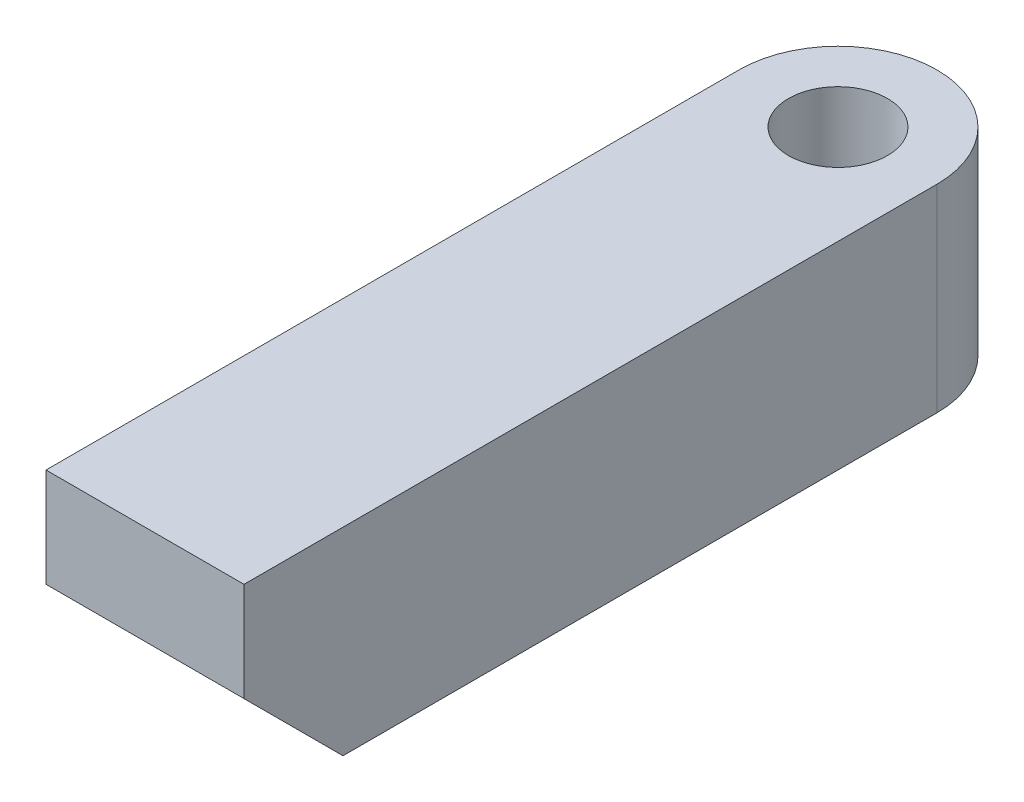
SolidWorks part; units mm, degrees
ref_plane "Front Plane" through (0, 0, 0) normal (0, 0, 1) x (1, 0, 0)
ref_plane "Top Plane" through (0, 0, 0) normal (0, 1, 0) x (1, 0, 0)
ref_plane "Right Plane" through (0, 0, 0) normal (1, 0, 0) x (0, 0, -1)
sketch "Sketch1" plane through (0, 0, 0) normal (0, 1, 0) x (1, 0, 0)
  line L1 (-5, -20) -> (5, -20)
  line L2 (-5, -20) -> (-5, 20)
  line L3 (-5, 20) -> (5, 20)
  line L4 (5, -20) -> (5, 20)
  line L5 (-5, -20) -> (5, 20) construction
  line L6 (-5, 20) -> (5, -20) construction
  point P0 (0, 0)
  dimension "D1" = 40
  dimension "D2" = 10
extrude "Boss-Extrude1" add sketch "Sketch1" along normal blind 10
hole_wizard "Ø5.0mm Dowel Hole1" positions "Sketch2" profile "Sketch3" hole size "Ø5.0" standard "ANSI Metric" end condition up to next
sketch "Sketch2" plane through (0, 10, 0) normal (0, 1, 0) x (1, 0, 0)
  point P0 (0, 15)
  dimension "D1" = 5
sketch "Sketch3" plane through (0, 10, -15) normal (1, 0, 0) x (0, 0, 1)
  line L0 (0, 0) -> (0, 10)
  line L1 (0, 10) -> (2.5, 10)
  line L2 (2.5, 10) -> (2.5, 0)
  line L5 (2.5, 0) -> (0, 0)
  line L11 (0, -6.35) -> (0, 107.95) construction
  dimension "Thru Hole Dia." = 5
  dimension "Thru Hole Depth" = 10
fillet "Fillet1" radius 5 2 edges at (5, 5, -20) (-5, 5, -20)
chamfer "Chamfer1" distance 5 angle 45 1 edges at (0, 0, 20)
